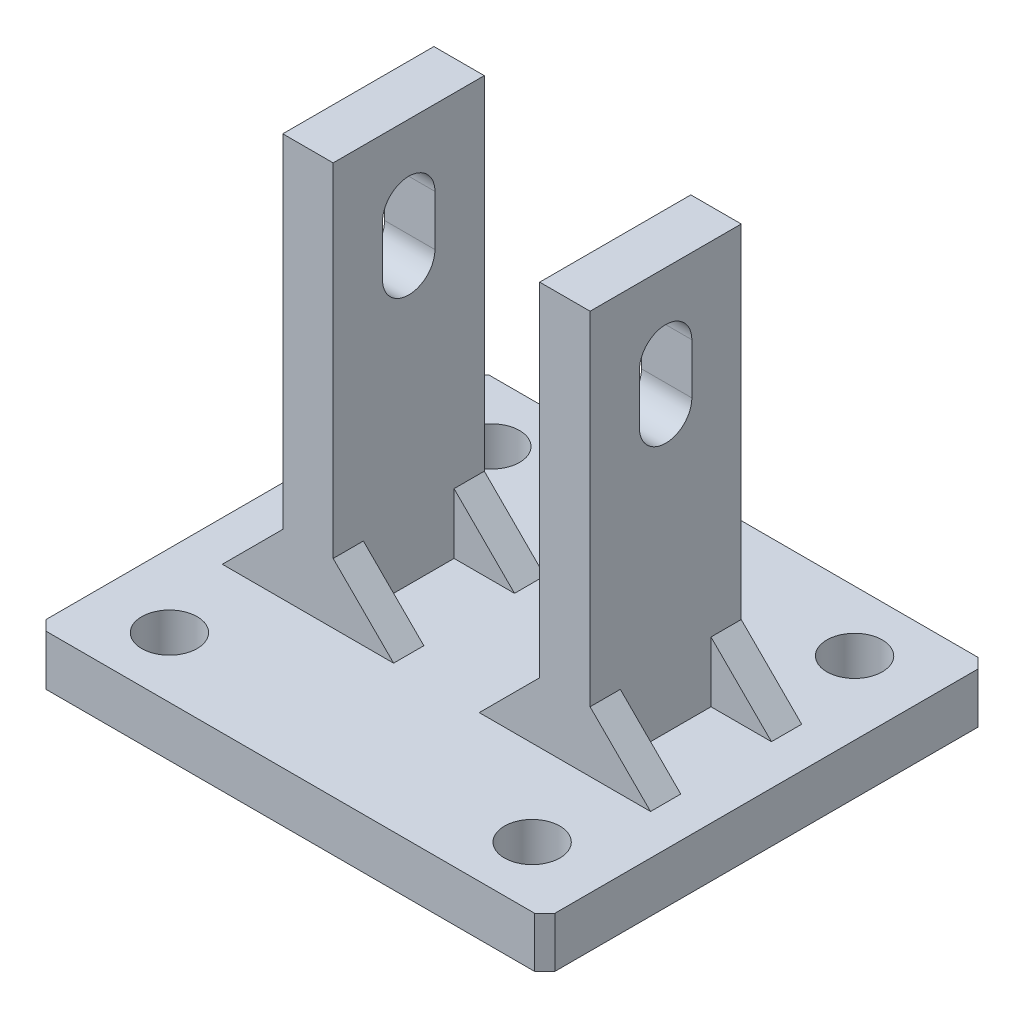
SolidWorks part; units mm, degrees
ref_plane "Front Plane" through (0, 0, 0) normal (0, 0, 1) x (1, 0, 0)
ref_plane "Top Plane" through (0, 0, 0) normal (0, 1, 0) x (1, 0, 0)
ref_plane "Right Plane" through (0, 0, 0) normal (1, 0, 0) x (0, 0, -1)
sketch "Sketch1" plane through (0, 0, 0) normal (0, 1, 0) x (1, 0, 0)
  line L1 (-18, 16) -> (18, 16) construction
  line L2 (-18, 16) -> (-18, -16) construction
  line L3 (-18, -16) -> (18, -16) construction
  line L4 (18, 16) -> (18, -16) construction
  line L5 (-18, 16) -> (18, -16) construction
  line L6 (-18, -16) -> (18, 16) construction
  line L7 (-25.25, 22) -> (25.25, 22)
  line L8 (-25.25, 22) -> (-25.25, -22)
  line L9 (-25.25, -22) -> (25.25, -22)
  line L10 (25.25, 22) -> (25.25, -22)
  line L11 (-25.25, 22) -> (25.25, -22) construction
  line L12 (-25.25, -22) -> (25.25, 22) construction
  circle A0 centre (-18, 16) radius 2.75
  circle A1 centre (18, 16) radius 2.75
  circle A2 centre (18, -16) radius 2.75
  circle A3 centre (-18, -16) radius 2.75
  point P0 (0, 0)
  point P10 (0, 0)
  dimension "D3" = 5.5
  dimension "D1" = 32
  dimension "D2" = 36
  dimension "D4" = 50.5
  dimension "D5" = 44
extrude "Boss-Extrude1" add sketch "Sketch1" along normal blind 5
sketch "Sketch3" plane through (0, 0, 22) normal (0, 0, 1) x (1, 0, 0)
  line L0 (-25.25, 5) -> (25.25, 5) construction
  line L1 (-15.25, 5) -> (-10.25, 5)
  line L2 (-15.25, 5) -> (-15.25, 45)
  line L3 (-15.25, 45) -> (-10.25, 45)
  line L4 (-10.25, 5) -> (-10.25, 45)
  line L6 (10.25, 5) -> (15.25, 5)
  line L7 (10.25, 5) -> (10.25, 45)
  line L8 (10.25, 45) -> (15.25, 45)
  line L9 (15.25, 5) -> (15.25, 45)
  line L10 (0, 0) -> (0, -8.4132) construction
  dimension "D1" = 5
  dimension "D2" = 20.5
  dimension "D3" = 40
extrude "Boss-Extrude2" add sketch "Sketch3" against normal blind 15 from offset 14.5 offset against normal yes
sketch "Sketch4" plane through (15.25, 0, 0) normal (1, 0, 0) x (0, 0, -1)
  line L0 (0, 37.5) -> (0, 32.5) construction
  line L1 (2.6, 37.5) -> (2.6, 32.5)
  line L2 (-2.6, 37.5) -> (-2.6, 32.5)
  line L3 (7.5, 45) -> (-7.5, 45) construction
  arc A0 (2.6, 37.5) -> (-2.6, 37.5) centre (0, 37.5) ccw
  arc A1 (-2.6, 32.5) -> (2.6, 32.5) centre (0, 32.5) ccw
  point P3 (0, 35)
  dimension "D2" = 2.6
  dimension "D1" = 5
  dimension "D3" = 10
extrude "Cut-Extrude1" cut sketch "Sketch4" against normal up to surface (30.5 mm away) up to face at (-15.25, 25, 0)
sketch "Sketch5" plane through (0, 0, 7.5) normal (0, 0, 1) x (1, 0, 0)
  line L0 (15.25, 11) -> (21.25, 5)
  line L1 (15.25, 5) -> (15.25, 45) construction
  line L2 (-25.25, 5) -> (25.25, 5) construction
  line L3 (21.25, 5) -> (15.25, 5)
  line L4 (15.25, 5) -> (15.25, 11)
  line L5 (0, -1.6344) -> (0, 7.9357) construction
  line L6 (-21.25, 5) -> (-15.25, 5)
  line L7 (-15.25, 11) -> (-21.25, 5)
  line L8 (-15.25, 5) -> (-15.25, 11)
  line L9 (10.25, 11) -> (4.25, 5)
  line L10 (10.25, 45) -> (10.25, 5) construction
  line L11 (4.25, 5) -> (10.25, 5)
  line L12 (10.25, 5) -> (15.25, 5) construction
  line L13 (10.25, 5) -> (10.25, 11)
  line L14 (-4.25, 5) -> (-10.25, 5)
  line L15 (-10.25, 11) -> (-4.25, 5)
  line L16 (-10.25, 5) -> (-10.25, 11)
  dimension "D1" = 45
  dimension "D2" = 6
  dimension "D3" = 45
  dimension "D4" = 6
extrude "Boss-Extrude3" add sketch "Sketch5" against normal blind 3
ref_plane "Plane1" through (0, 0, 0) normal (0, 0, -1) x (-1, 0, 0)
mirror "Mirror1" about plane through (0, 0, 0) normal (0, 0, -1) of "Boss-Extrude3"
chamfer "Chamfer2" distance 1 angle 45 4 edges at (25.25, 2.5, 22) (-25.25, 2.5, -22) (25.25, 2.5, -22) (-25.25, 2.5, 22)
